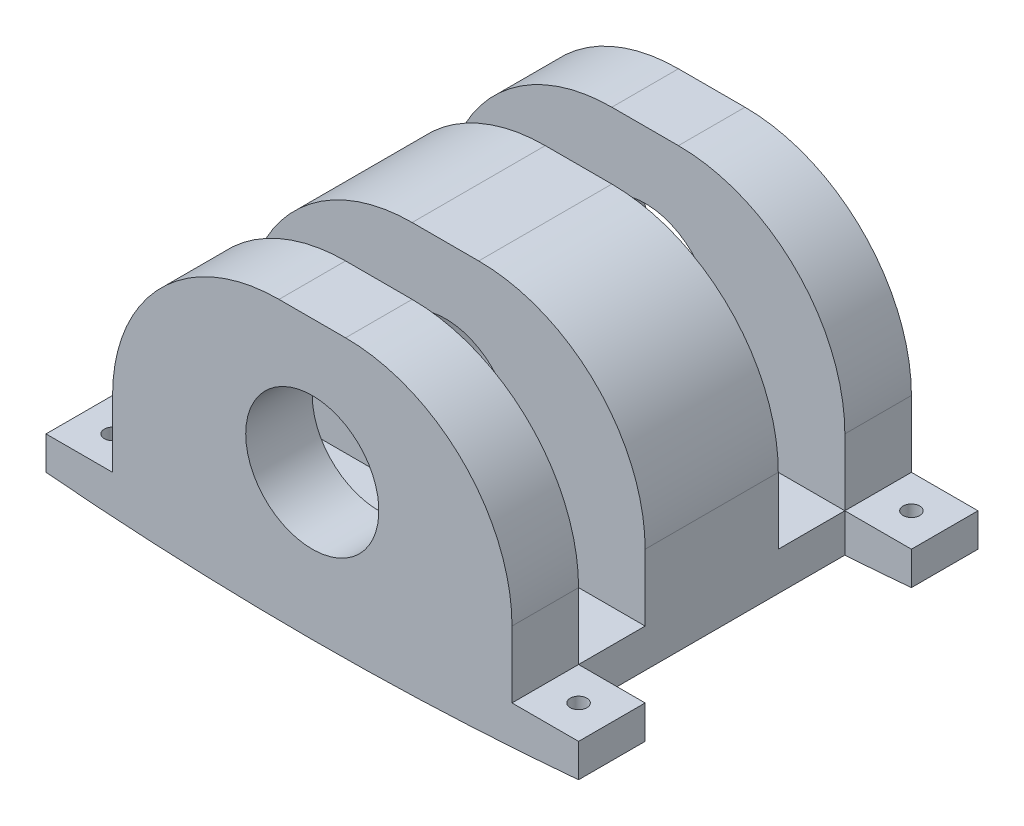
SolidWorks part; units mm, degrees
ref_plane "Front Plane" through (0, 0, 0) normal (0, 0, 1) x (1, 0, 0)
ref_plane "Top Plane" through (0, 0, 0) normal (0, 1, 0) x (1, 0, 0)
ref_plane "Right Plane" through (0, 0, 0) normal (1, 0, 0) x (0, 0, -1)
sketch "Sketch1" plane through (0, 0, 0) normal (0, 0, 1) x (1, 0, 0)
  line L1 (-76.2, -50.8) -> (76.2, -50.8) construction
  line L2 (-76.2, -38.1) -> (-76.2, -12.7)
  line L3 (-12.7, 50.8) -> (12.7, 50.8)
  line L4 (76.2, -38.1) -> (76.2, -12.7)
  line L5 (-76.2, -50.8) -> (76.2, 50.8) construction
  line L6 (-76.2, 50.8) -> (76.2, -50.8) construction
  line L7 (-76.2, -50.8) -> (-101.6, -50.8) construction
  line L9 (-76.2, -38.1) -> (-101.6, -38.1)
  line L10 (-101.6, -50.8) -> (-101.6, -38.1)
  line L11 (76.2, -50.8) -> (101.6, -50.8) construction
  line L13 (76.2, -38.1) -> (101.6, -38.1)
  line L14 (101.6, -50.8) -> (101.6, -38.1)
  arc A0 (76.2, -12.7) -> (12.7, 50.8) centre (12.7, -12.7) ccw
  arc A1 (-12.7, 50.8) -> (-76.2, -12.7) centre (-12.7, -12.7) ccw
  circle A2 centre (0, 0) radius 25.4
  arc A3 (-101.6, -50.8) -> (101.6, -50.8) centre (0, 1094.7031) ccw
  point P0 (0, 0)
  dimension "D3" = 63.5
  dimension "D8" = 50.8
  dimension "D9" = 1150
  dimension "D1" = 152.4
  dimension "D2" = 101.6
  dimension "D4" = 12.7
  dimension "D5" = 12.7
  dimension "D6" = 25.4
  dimension "D7" = 25.4
extrude "Boss-Extrude1" add sketch "Sketch1" along normal blind 152.4
sketch "Sketch3" plane through (0, 0, 0) normal (1, 0, 0) x (0, 0, -1)
  line L0 (-152.4, -38.1) -> (0, -38.1) construction
  line L1 (-127, -38.1) -> (-101.6, -38.1)
  line L2 (-127, -38.1) -> (-127, 50.8)
  line L3 (-127, 50.8) -> (-101.6, 50.8)
  line L4 (-101.6, -38.1) -> (-101.6, 50.8)
  line L5 (-152.4, 50.8) -> (0, 50.8) construction
  line L6 (-152.4, 50.8) -> (-152.4, -12.7) construction
  line L7 (-50.8, -38.1) -> (-25.4, -38.1)
  line L8 (-50.8, -38.1) -> (-50.8, 50.8)
  line L9 (-50.8, 50.8) -> (-25.4, 50.8)
  line L10 (-25.4, -38.1) -> (-25.4, 50.8)
  dimension "D1" = 25.4
  dimension "D2" = 25.4
  dimension "D3" = 50.8
  dimension "D4" = 25.4
extrude "Cut-Extrude1" cut sketch "Sketch3" against normal through all both and the other way through all
sketch "Sketch4" plane through (0, -38.1, 0) normal (0, 1, 0) x (1, 0, 0)
  line L0 (-101.6, -152.4) -> (-101.6, 0) construction
  line L1 (101.6, -152.4) -> (101.6, 0) construction
  line L2 (-76.2, 0) -> (-101.6, 0) construction
  line L3 (-76.2, -101.6) -> (-76.2, -50.8) construction
  line L4 (-101.6, -25.4) -> (-76.2, -25.4)
  line L5 (-101.6, -25.4) -> (-101.6, -127)
  line L6 (-101.6, -127) -> (-76.2, -127)
  line L7 (-76.2, -25.4) -> (-76.2, -127)
  line L8 (-76.2, -152.4) -> (-101.6, -152.4) construction
  line L9 (0, -55) -> (0, 55) construction
  line L10 (101.6, -127) -> (76.2, -127)
  line L11 (76.2, -25.4) -> (76.2, -127)
  line L12 (101.6, -25.4) -> (76.2, -25.4)
  line L13 (101.6, -25.4) -> (101.6, -127)
  point P0 (-88.9, -12.7)
  point P2 (-88.9, -139.7)
  point P3 (88.9, -12.7)
  point P5 (88.9, -139.7)
  dimension "D1" = 12.7
  dimension "D2" = 12.7
  dimension "D3" = 12.7
  dimension "D4" = 25.4
  dimension "D5" = 25.4
hole_wizard "1/4 (0.25) Diameter Hole1" positions "Sketch5" profile "Sketch6" hole size "1/4" standard "ANSI Inch" end condition through all
sketch "Sketch5" plane through (0, -38.1, 0) normal (0, 1, 0) x (1, 0, 0)
  point P3 (-88.9, -12.7)
  point P6 (-88.9, -139.7)
  point P9 (88.9, -12.7)
  point P15 (88.9, -139.7)
sketch "Sketch6" plane through (-88.9, -38.1, 12.7) normal (1, 0, 0) x (0, 0, 1)
  line L0 (0, 0) -> (0, 17.1969)
  line L1 (0, 17.1969) -> (3.175, 17.1969)
  line L2 (3.175, 17.1969) -> (3.175, 0)
  line L5 (3.175, 0) -> (0, 0)
  line L11 (0, -6.35) -> (0, 107.95) construction
  dimension "Thru Hole Dia." = 6.35
  dimension "Thru Hole Depth" = 17.1969
extrude "Cut-Extrude2" cut sketch "Sketch4" against normal through all
